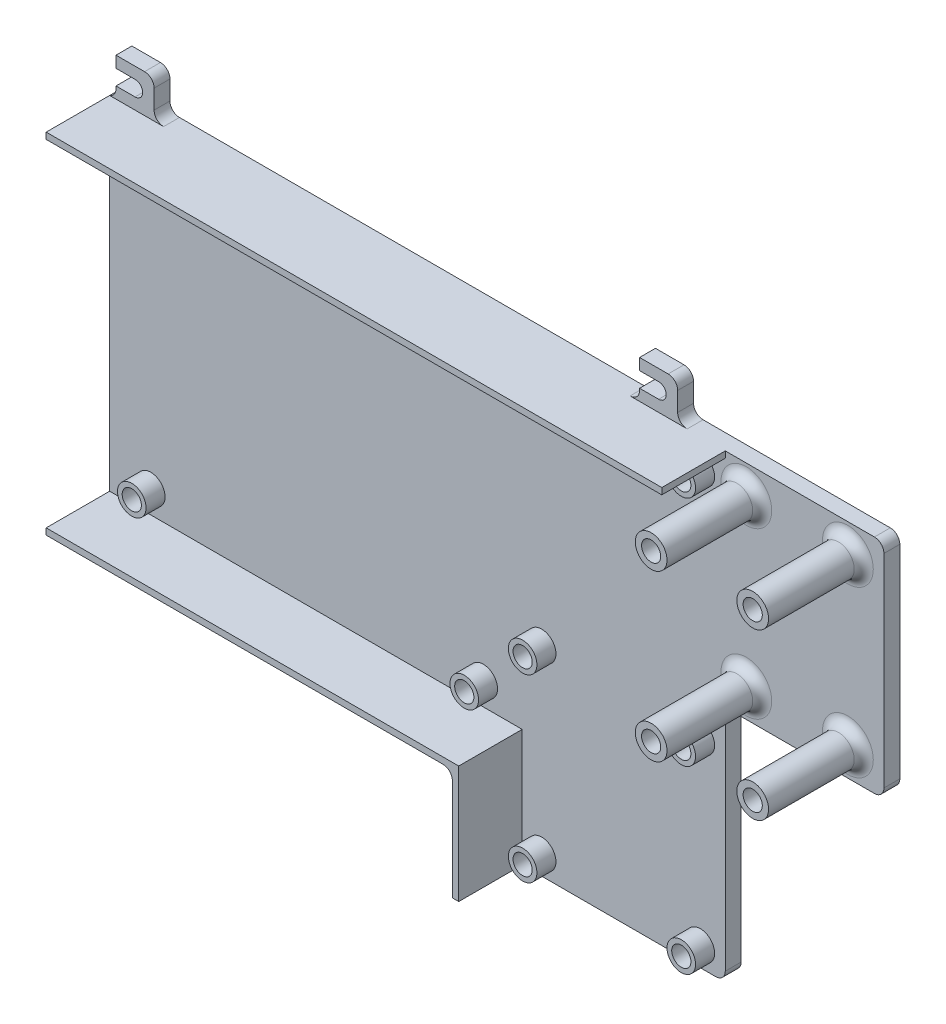
SolidWorks part; units mm, degrees
material "ABS"
ref_plane "X-Y Datum" through (0, 0, 0) normal (0, 0, 1) x (1, 0, 0)
ref_plane "X-Z Datum" through (0, 0, 0) normal (0, 1, 0) x (1, 0, 0)
ref_plane "Y-Z Datum" through (0, 0, 0) normal (1, 0, 0) x (0, 0, -1)
sketch "Sketch1" plane through (0, 0, 0) normal (0, 0, 1) x (1, 0, 0)
  line L1 (-167.3248, 270.3744) -> (-39.3248, 270.3744)
  line L2 (-167.3248, 270.3744) -> (-167.3248, 160.3744)
  line L3 (-167.3248, 160.3744) -> (-39.3248, 160.3744)
  line L4 (-39.3248, 270.3744) -> (-39.3248, 160.3744)
  line L5 (-39.3248, 270.3744) -> (26.6752, 270.3744)
  line L6 (-39.3248, 270.3744) -> (-39.3248, 125.3744)
  line L7 (-39.3248, 125.3744) -> (26.6752, 125.3744)
  line L8 (26.6752, 270.3744) -> (26.6752, 125.3744)
  line L10 (26.6752, 125.3744) -> (26.6752, 195.3744)
  line L13 (26.6752, 270.3744) -> (76.6752, 270.3744)
  line L14 (26.6752, 270.3744) -> (26.6752, 200.3744)
  line L15 (26.6752, 200.3744) -> (76.6752, 200.3744)
  line L16 (76.6752, 270.3744) -> (76.6752, 200.3744)
  dimension "D1" = 110
  dimension "D2" = 128
  dimension "D3" = 66
  dimension "D4" = 145
  dimension "D7" = 70
  dimension "D8" = 50
extrude "Boss-Extrude1" add sketch "Sketch1" along normal blind 5 contours L4 L1 L2 L3 | L8 L5 L4 L6 L7 | L8 region at (-103.3248, 215.3744, 0) region at (-6.3248, 197.8744, 0) region at (51.6752, 235.3744, 0)
sketch "Sketch2" plane through (0, 0, 5) normal (0, 0, 1) x (1, 0, 0)
  circle A1 centre (-154.3548, 262.4914) radius 3.025
  circle A2 centre (-154.3548, 262.4914) radius 4.5
  circle A6 centre (-154.3548, 169.5274) radius 4.5
  circle A7 centre (-154.3548, 169.5274) radius 3.025
  circle A8 centre (-31.1818, 131.5554) radius 4.5
  circle A9 centre (-31.1818, 131.5554) radius 3.025
  circle A10 centre (18.8182, 131.5554) radius 3.025
  circle A11 centre (18.8182, 131.5554) radius 4.5
  circle A12 centre (18.8182, 188.3054) radius 3.025
  circle A13 centre (18.8182, 188.3054) radius 4.5
  circle A14 centre (-31.1818, 188.3054) radius 4.5
  circle A15 centre (-31.1818, 188.3054) radius 3.025
  circle A16 centre (-31.1818, 261.5554) radius 3.025
  circle A17 centre (-31.1818, 261.5554) radius 4.5
  circle A18 centre (18.8182, 261.5554) radius 4.5
  circle A19 centre (18.8182, 261.5554) radius 3.025
  circle A21 centre (-49.5798, 169.5274) radius 2.1 construction
  circle A23 centre (-49.5798, 169.5274) radius 2.1
  circle A24 centre (-49.5798, 262.4914) radius 4.4118
  circle A25 centre (-49.5798, 262.4914) radius 3.025
  circle A26 centre (-49.5798, 169.5274) radius 4.5
  circle A27 centre (-49.5798, 169.5274) radius 3.025
  point P0 (-154.3548, 262.4914)
  point P1 (-44.4998, 262.4914)
  point P3 (-44.4998, 169.5274)
  point P5 (-154.3548, 169.5274)
  point P7 (18.8182, 261.5554)
  point P9 (-31.1818, 261.5554)
  point P11 (-31.1818, 188.3054)
  point P13 (-31.1818, 131.5554)
  point P15 (18.8182, 131.5554)
  point P17 (18.8182, 188.3054)
  dimension "D1" = 6.05
  dimension "D2" = 9
extrude "Boss-Extrude2" add sketch "Sketch2" along normal blind 6 contours A26 A27 | A14 A15 | A8 A9 | A11 A10 | A13 A12 | A18 A19 | A24 A25 | A2 A1 | A6 A7 | A17 A16 region at (-158.7275, 262.4914, 5) region at (-158.7275, 169.5274, 5) region at (-35.5545, 131.5554, 5) region at (14.4455, 131.5554, 5) region at (14.4455, 188.3054, 5) region at (-35.5545, 188.3054, 5) region at (-35.5545, 261.5554, 5) region at (14.4455, 261.5554, 5) region at (-53.8667, 262.4914, 5) region at (-53.9525, 169.5274, 5)
sketch "Sketch3" plane through (0, 0, 5) normal (0, 0, 1) x (1, 0, 0)
  line L0 (26.6752, 200.3744) -> (26.6752, 125.3744) construction
  line L1 (-167.3248, 270.3744) -> (26.6752, 270.3744)
  line L2 (-167.3248, 270.3744) -> (-167.3248, 268.3744)
  line L3 (-167.3248, 268.3744) -> (26.6752, 268.3744)
  line L4 (26.6752, 270.3744) -> (26.6752, 268.3744)
  line L6 (-167.3248, 160.3744) -> (-39.3248, 160.3744)
  line L7 (-167.3248, 160.3744) -> (-167.3248, 162.3744)
  line L8 (-167.3248, 162.3744) -> (-39.3248, 162.3744)
  line L9 (-39.3248, 160.3744) -> (-39.3248, 162.3744)
  line L10 (-39.3248, 125.3744) -> (-37.3248, 125.3744)
  line L11 (-39.3248, 125.3744) -> (-39.3248, 162.3744)
  line L12 (-39.3248, 162.3744) -> (-37.3248, 162.3744)
  line L13 (-37.3248, 125.3744) -> (-37.3248, 162.3744)
  line M14 (-167.3248, 160.3744) -> (-39.3248, 160.3744)
  line M15 (-39.3248, 160.3744) -> (-39.3248, 125.3744)
  line M19 (26.6752, 125.3744) -> (26.6752, 200.3744)
  line M20 (76.6752, 270.3744) -> (-167.3248, 270.3744)
  line M21 (-167.3248, 270.3744) -> (-167.3248, 160.3744)
  dimension "D1" = 2
  dimension "D2" = 2
  dimension "D3" = 2
extrude "Boss-Extrude3" add sketch "Sketch3" along normal blind 20 contours L13 L12 L9 M15 | L9 L8 M14 M21 | L3 M21 M19 M20 region at (-103.3248, 161.3744, 5) region at (-70.3248, 269.3744, 5) region at (-38.3248, 143.8744, 5)
sketch "Sketch6" plane through (0, 0, 0) normal (0, 0, -1) x (-1, 0, 0)
  line L0 (167.3248, 160.3744) -> (39.3248, 160.3744) construction
  line L1 (137.3248, 160.3744) -> (125.3248, 160.3744)
  line L2 (137.3248, 160.3744) -> (137.3248, 148.3744)
  line L3 (137.3248, 148.3744) -> (125.3248, 148.3744)
  line L4 (125.3248, 160.3744) -> (125.3248, 148.3744)
  line L5 (-26.6752, 270.3744) -> (167.3248, 270.3744) construction
  line L6 (165.3248, 270.3744) -> (153.3248, 270.3744)
  line L7 (165.3248, 270.3744) -> (165.3248, 282.3744)
  line L8 (165.3248, 282.3744) -> (153.3248, 282.3744)
  line L9 (153.3248, 270.3744) -> (153.3248, 282.3744)
  line L11 (51.3248, 160.3744) -> (39.3248, 160.3744)
  line L12 (51.3248, 160.3744) -> (51.3248, 148.3744)
  line L13 (51.3248, 148.3744) -> (39.3248, 148.3744)
  line L14 (39.3248, 160.3744) -> (39.3248, 148.3744)
  line L15 (131.3248, 160.3744) -> (131.3248, 148.3744) construction
  line L16 (0.3248, 270.3744) -> (-11.6752, 270.3744)
  line L17 (0.3248, 270.3744) -> (0.3248, 282.3744)
  line L18 (0.3248, 282.3744) -> (-11.6752, 282.3744)
  line L19 (-11.6752, 270.3744) -> (-11.6752, 282.3744)
  line L20 (167.3248, 162.3744) -> (167.3248, 160.3744) construction
  line L21 (159.3248, 282.3744) -> (159.3248, 270.3744) construction
  line L22 (-5.6752, 282.3744) -> (-5.6752, 270.3744) construction
  line L23 (45.3248, 160.3744) -> (45.3248, 148.3744) construction
  line L24 (167.3248, 268.3744) -> (167.3248, 162.3744) construction
  line L27 (-26.6752, 200.3744) -> (-26.6752, 125.3744) construction
  line L29 (39.3248, 125.3744) -> (39.3248, 160.3744) construction
  circle A0 centre (131.3248, 154.3744) radius 2 construction
  circle A1 centre (45.3248, 154.3744) radius 2 construction
  circle A2 centre (-5.6752, 276.3744) radius 2 construction
  circle A3 centre (159.3248, 276.3744) radius 2 construction
  dimension "D1" = 4
  dimension "D2" = 12
  dimension "D3" = 12
  dimension "D4" = 30
  dimension "D5" = 2
  dimension "D6" = 15
extrude "Boss-Extrude5" add sketch "Sketch6" against normal blind 5
hole_wizard "M4 Clearance Hole1" positions "Sketch9" profile "Sketch8" hole size "M4" standard "ANSI Metric" end condition through all
sketch "Sketch9" plane through (0, 0, 5) normal (0, 0, 1) x (1, 0, 0)
  line L0 (-131.3248, 160.3744) -> (-131.3248, 148.3744) construction
  point P0 (-131.3248, 154.3744)
  point P4 (-159.3248, 276.3744)
  point P7 (5.6752, 276.3744)
  point P10 (-45.3248, 154.3744)
sketch "Sketch8" plane through (-131.3248, 154.3744, 5) normal (1, 0, 0) x (0, -1, 0)
  line L0 (0, 0) -> (0, 5)
  line L1 (0, 5) -> (2.4, 5)
  line L2 (2.4, 5) -> (2.4, 0)
  line L5 (2.4, 0) -> (0, 0)
  line L11 (0, -6.35) -> (0, 107.95) construction
  dimension "Thru Hole Dia." = 4.8
  dimension "Thru Hole Depth" = 5
sketch "Sketch10" plane through (0, 0, 5) normal (0, 0, 1) x (1, 0, 0)
  line L0 (-159.3248, 278.7744) -> (-165.3248, 278.7744)
  line L1 (-159.3248, 282.3744) -> (-159.3248, 270.3744) construction
  line L2 (-165.3248, 270.3744) -> (-165.3248, 282.3744) construction
  line L3 (-159.3248, 273.9744) -> (-165.3248, 273.9744)
  line L4 (-131.3248, 156.7744) -> (-137.3248, 156.7744)
  line L5 (-131.3248, 160.3744) -> (-131.3248, 148.3744) construction
  line L6 (-137.3248, 160.3744) -> (-137.3248, 148.3744) construction
  line L7 (-131.3248, 151.9744) -> (-137.3248, 151.9744)
  line L8 (-45.3248, 156.7744) -> (-51.3248, 156.7744)
  line L9 (-45.3248, 160.3744) -> (-45.3248, 148.3744) construction
  line L10 (-51.3248, 160.3744) -> (-51.3248, 148.3744) construction
  line L11 (-45.3248, 151.9744) -> (-51.3248, 151.9744)
  line L12 (5.6752, 278.7744) -> (-0.3248, 278.7744)
  line L13 (5.6752, 282.3744) -> (5.6752, 270.3744) construction
  line L14 (-0.3248, 270.3744) -> (-0.3248, 282.3744) construction
  line L15 (5.6752, 273.9744) -> (-0.3248, 273.9744)
  line L16 (-51.3248, 148.3744) -> (-51.3248, 160.3744) construction
  line L17 (-51.3248, 148.3744) -> (-51.3248, 160.3744)
  line L20 (-137.3248, 160.3744) -> (-137.3248, 148.3744)
  line L21 (-137.3248, 148.3744) -> (-125.3248, 148.3744)
  line L22 (-125.3248, 148.3744) -> (-125.3248, 160.3744)
  line L23 (-125.3248, 160.3744) -> (-137.3248, 160.3744)
  line L24 (-137.3248, 160.3744) -> (-137.3248, 148.3744)
  line L25 (-137.3248, 148.3744) -> (-125.3248, 148.3744)
  line L26 (-125.3248, 148.3744) -> (-125.3248, 160.3744)
  line L27 (-125.3248, 160.3744) -> (-137.3248, 160.3744)
  line L28 (-0.3248, 282.3744) -> (-0.3248, 270.3744)
  line L29 (-0.3248, 270.3744) -> (11.6752, 270.3744)
  line L30 (26.6752, 125.3744) -> (26.6752, 200.3744)
  line L34 (26.6752, 268.3744) -> (-167.3248, 268.3744)
  line L35 (-167.3248, 268.3744) -> (-167.3248, 162.3744)
  line L36 (-167.3248, 162.3744) -> (-37.3248, 162.3744)
  line L37 (-37.3248, 162.3744) -> (-37.3248, 125.3744)
  line L38 (26.6752, 200.3744) -> (76.6752, 200.3744)
  line L48 (26.6752, 268.3744) -> (-167.3248, 268.3744)
  line L49 (-167.3248, 268.3744) -> (-167.3248, 162.3744)
  line L50 (-167.3248, 162.3744) -> (-37.3248, 162.3744)
  line L51 (-37.3248, 162.3744) -> (-37.3248, 125.3744)
  line L58 (11.6752, 270.3744) -> (11.6752, 282.3744)
  line L59 (11.6752, 282.3744) -> (-0.3248, 282.3744)
  line L60 (-0.3248, 282.3744) -> (-0.3248, 270.3744)
  line L61 (-0.3248, 270.3744) -> (11.6752, 270.3744)
  line L62 (11.6752, 270.3744) -> (11.6752, 282.3744)
  line L63 (11.6752, 282.3744) -> (-0.3248, 282.3744)
  line L64 (-165.3248, 282.3744) -> (-165.3248, 270.3744)
  line L65 (-165.3248, 270.3744) -> (-153.3248, 270.3744)
  line L66 (-153.3248, 270.3744) -> (-153.3248, 282.3744)
  line L67 (-153.3248, 282.3744) -> (-165.3248, 282.3744)
  line L68 (-165.3248, 282.3744) -> (-165.3248, 270.3744)
  line L69 (-165.3248, 270.3744) -> (-153.3248, 270.3744)
  line L70 (-153.3248, 270.3744) -> (-153.3248, 282.3744)
  line L71 (-153.3248, 282.3744) -> (-165.3248, 282.3744)
  line L80 (26.6752, 200.3744) -> (76.6752, 200.3744)
  line L82 (76.6752, 200.3744) -> (76.6752, 270.3744)
  line L84 (76.6752, 200.3744) -> (76.6752, 270.3744)
  line L85 (76.6752, 270.3744) -> (26.6752, 270.3744)
  line L86 (76.6752, 270.3744) -> (26.6752, 270.3744)
  line L87 (26.6752, 270.3744) -> (26.6752, 268.3744)
  line L89 (-37.3248, 125.3744) -> (26.6752, 125.3744)
  line L90 (-37.3248, 125.3744) -> (26.6752, 125.3744)
  line L94 (26.6752, 270.3744) -> (26.6752, 268.3744)
  line L95 (26.6752, 125.3744) -> (26.6752, 200.3744)
  circle A0 centre (-159.3248, 276.3744) radius 2.4 construction
  circle A1 centre (-131.3248, 154.3744) radius 2.4 construction
  circle A2 centre (-45.3248, 154.3744) radius 2.4 construction
  circle A3 centre (5.6752, 276.3744) radius 2.4 construction
  circle A4 centre (-159.3248, 276.3744) radius 2.4
  circle A5 centre (5.6752, 276.3744) radius 2.4
  circle A10 centre (-45.3248, 154.3744) radius 2.4
  circle A11 centre (-131.3248, 154.3744) radius 2.4
  circle M29 centre (-131.3248, 154.3744) radius 2.4
  line M30 (-137.3248, 160.3744) -> (-137.3248, 148.3744)
  dimension "D1" = 0
  dimension "D2" = 0
  dimension "D3" = 0
  dimension "D4" = 0
extrude "Cut-Extrude1" cut sketch "Sketch10" against normal through all contours L7 L4 M29 M30 | A4 L0 L68 L3 | A5 L12 L60 L15 | A10 L8 L11 region at (-163.2324, 276.3744, 5) region at (-135.2324, 154.3744, 5) region at (-49.2324, 154.3744, 5) region at (1.7676, 276.3744, 5)
fillet "Fillet2" radius 3 11 edges at (-153.3248, 282.3744, 2.5) (-153.3248, 270.3744, 2.5) (-165.3248, 270.3744, 2.5) (-0.3248, 270.3744, 2.5) (11.6752, 270.3744, 2.5) (11.6752, 282.3744, 2.5) (-125.3248, 148.3744, 2.5) (-137.3248, 160.3744, 2.5) (-125.3248, 160.3744, 2.5) (-51.3248, 160.3744, 2.5) (-39.3248, 148.3744, 2.5)
fillet "Fillet3" radius 3 5 edges at (-39.3248, 160.3744, 15) (26.6752, 200.3744, 2.5) (76.6752, 270.3744, 2.5) (76.6752, 200.3744, 2.5) (26.6752, 125.3744, 2.5)
sketch "Sketch11" plane through (0, 0, 5) normal (0, 0, 1) x (1, 0, 0)
  circle A0 centre (33.3182, 261.3744) radius 5
  circle A1 centre (65.3182, 261.3744) radius 3.025
  circle A2 centre (65.3182, 209.3744) radius 3.025
  circle A3 centre (33.3182, 209.3744) radius 3.025
  circle A4 centre (33.3182, 261.3744) radius 3.025
  circle A5 centre (65.3182, 261.3744) radius 5
  circle A6 centre (65.3182, 209.3744) radius 5
  circle A7 centre (33.3182, 209.3744) radius 5
  dimension "D1" = 6.05
  dimension "D2" = 10
extrude "Boss-Extrude6" add sketch "Sketch11" along normal blind 30
fillet "Fillet4" radius 3 4 edges at (70.3182, 261.3744, 5) (38.3182, 261.3744, 5) (38.3182, 209.3744, 5) (70.3182, 209.3744, 5)
equation "\"16mmm\"=20"
